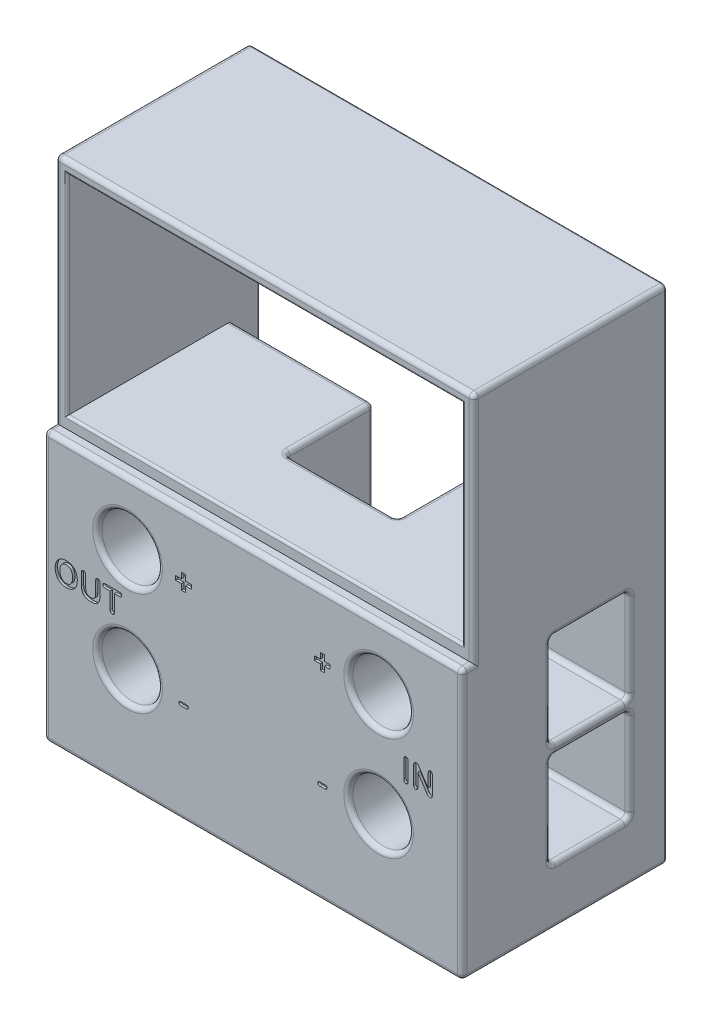
SolidWorks part; units mm, degrees
ref_plane "Front Plane" through (0, 0, 0) normal (0, 0, 1) x (1, 0, 0)
ref_plane "Top Plane" through (0, 0, 0) normal (0, 1, 0) x (1, 0, 0)
ref_plane "Right Plane" through (0, 0, 0) normal (1, 0, 0) x (0, 0, -1)
sketch "Sketch2" plane through (0, 0, 0) normal (0, 0, 1) x (1, 0, 0)
  line L0 (0, 32.5) -> (0, 0) construction
  line L1 (43.9999, -54) -> (-43.9999, -54)
  line L2 (43.9999, -54) -> (43.9999, 54)
  line L3 (43.9999, 54) -> (-43.9999, 54)
  line L4 (-43.9999, -54) -> (-43.9999, 54)
  line L5 (43.9999, -54) -> (-43.9999, 54) construction
  line L6 (43.9999, 54) -> (-43.9999, -54) construction
  line L9 (0, 0) -> (0, -20.5) construction
  line L10 (-31.75, 43.125) -> (31.75, 43.125)
  line L11 (-31.75, 43.125) -> (-31.75, 21.875)
  line L12 (-31.75, 21.875) -> (31.75, 21.875)
  line L13 (31.75, 43.125) -> (31.75, 21.875)
  line L14 (-31.75, 43.125) -> (31.75, 21.875) construction
  line L15 (-31.75, 21.875) -> (31.75, 43.125) construction
  line L16 (27, -31.625) -> (-27, -31.625)
  line L17 (27, -31.625) -> (27, -9.375)
  line L18 (27, -9.375) -> (-27, -9.375)
  line L19 (-27, -31.625) -> (-27, -9.375)
  line L20 (27, -31.625) -> (-27, -9.375) construction
  line L21 (27, -9.375) -> (-27, -31.625) construction
  circle A0 centre (-27, -9.375) radius 6.5
  circle A1 centre (27, -9.375) radius 6.5
  circle A2 centre (27, -31.625) radius 6.5
  circle A3 centre (-27, -31.625) radius 6.5
  point P0 (0, 0)
  point P5 (0, 32.5)
  point P26 (0, -20.5)
  dimension "D4" = 13
  dimension "D1" = 108
  dimension "D2" = 21.25
  dimension "D3" = 63.5
  dimension "D5" = 22.25
  dimension "D6" = 54
  dimension "D7" = 87.9997
  dimension "D8" = 32.5
  dimension "D9" = 20.5
extrude "Boss-Extrude1" add sketch "Sketch2" against normal blind 46 contours L4 L1 L2 L3 A3 L19 A0 L18 A1 L17 A2 L16 L10 L13 L12 L11 | A3 L16 A2 L17 A1 L18 A0 L19 region at (0, -1.6874, 0) region at (0, -20.5, 0)
sketch "Sketch3" plane through (0, 0, 0) normal (1, 0, 0) x (0, 0, -1)
  line L0 (46, -54) -> (0, -54) construction
  line L1 (46, 54) -> (0.0001, 54)
  line L2 (46, 54) -> (46, -54)
  line L3 (46, -54) -> (0.0001, -54)
  line L4 (0.0001, 54) -> (0.0001, -54)
  line L5 (46, 54) -> (0.0001, -54) construction
  line L6 (46, -54) -> (0.0001, 54) construction
  line L7 (46, -54) -> (46, 54) construction
  line L8 (23, -15.875) -> (23, -25.125) construction
  line L9 (30.5308, -2.875) -> (30.5308, -15.875) construction
  line L18 (34, 0.625) -> (34, -19.375)
  line L19 (34, -9.375) -> (27.5, -9.375) construction
  line L20 (36, -19.375) -> (34, -19.375)
  line L21 (36, 0.625) -> (36, -19.375)
  line L22 (36, 0.625) -> (34, 0.625)
  line L23 (34, -19.375) -> (34, 0.625)
  line L24 (19, 0.625) -> (34, 0.625)
  line L25 (19, -19.375) -> (19, 0.625)
  line L26 (19, -19.375) -> (34, -19.375)
  line L27 (46, -2.875) -> (0, -2.875) construction
  line L28 (0, -15.875) -> (46, -15.875) construction
  line L29 (46, -25.125) -> (0, -25.125) construction
  line L30 (0.0001, -20.5) -> (46, -20.5) construction
  line L31 (34, -31.625) -> (27.5, -31.625) construction
  line L32 (30.5308, -38.125) -> (30.5308, -25.125) construction
  line L33 (19, -21.625) -> (34, -21.625)
  line L34 (19, -21.625) -> (19, -41.625)
  line L35 (19, -41.625) -> (34, -41.625)
  line L36 (34, -21.625) -> (34, -41.625)
  line L37 (36, -41.625) -> (34, -41.625)
  line L38 (36, -41.625) -> (36, -21.625)
  line L39 (36, -21.625) -> (34, -21.625)
  line L40 (34, -41.625) -> (34, -21.625)
  arc A1 (34, -17.625) -> (34, -1.125) centre (35.9856, -9.375) cw
  arc A2 (34, -23.375) -> (34, -39.875) centre (35.9856, -31.625) ccw
  point P0 (23, 0)
  point P8 (30.5308, -9.375)
  point P19 (23, -20.5)
  point P48 (23, -41)
  dimension "D4" = 6.5
  dimension "D7" = 1.75
  dimension "D1" = 108
  dimension "D2" = 20
  dimension "D3" = 45.9999
  dimension "D5" = 2
  dimension "D6" = 15
  dimension "D8" = 10
sketch "Sketch4" plane through (0, 0, -46) normal (0, 0, -1) x (-1, 0, 0)
  line L1 (-31.75, 21.875) -> (31.75, 21.875)
  line L2 (-31.75, 21.875) -> (-31.75, 43.125)
  line L3 (-31.75, 43.125) -> (31.75, 43.125)
  line L4 (31.75, 21.875) -> (31.75, 43.125)
extrude "Boss-Extrude2" add sketch "Sketch4" against normal offset from surface (44 mm away) 2 up to face at (-20.5, -9.375, 0)
sketch "Sketch5" plane through (0, 0, -46) normal (0, 0, -1) x (-1, 0, 0)
  circle A0 centre (-27, -9.375) radius 6.5
  circle A1 centre (-27, -31.625) radius 6.5
  circle A2 centre (27, -31.625) radius 6.5
  circle A3 centre (27, -9.375) radius 6.5
  circle A5 centre (-27, -9.375) radius 6.5 construction
extrude "Boss-Extrude3" add sketch "Sketch5" against normal blind 10
sketch "Sketch7" plane through (0, 0, 0) normal (0, 0, 1) x (1, 0, 0)
  line L0 (-45, -54) -> (45, 54) construction
  line L1 (-45, 54) -> (45, 54)
  line L2 (-45, 54) -> (-45, -54)
  line L3 (-45, -54) -> (45, -54)
  line L4 (45, 54) -> (45, -54)
  line L5 (43.9999, 54) -> (-43.9999, 54) construction
  line L7 (-43.9999, 54) -> (43.9999, 54)
  line L8 (-43.9999, 54) -> (-43.9999, -54)
  line L9 (-43.9999, -54) -> (43.9999, -54)
  line L10 (43.9999, 54) -> (43.9999, -54)
  line M10 (-43.9999, 54) -> (-43.9999, -54)
  line M12 (43.9999, -54) -> (43.9999, 54)
  dimension "D1" = 90
extrude "Boss-Extrude4" add sketch "Sketch7" against normal up to surface (46 mm away) contours L0 L3 L4 M12 | L2 L0 L1 M10 | L10 L0 L1 | L0 L3 L8 region at (-44.5009, 0.2995, 0) region at (-44.3332, -53.5999, 0) region at (44.3332, 53.5999, 0) region at (44.5009, -0.2995, 0) up to face at (0, 0, -46)
extrude "Cut-Extrude1" cut sketch "Sketch3" along normal blind 28 from surface contours L18 A1 L24 L25 L26 | L21 L22 L18 L23 L20 | A2 L36 L33 L34 L35 | L40 A2 | L38 L39 L36 L40 L37 | A1 L23 region at (0, -9.375, -35) region at (0, -9.375, -24.7667) region at (0, -9.375, -31.2897) region at (0, -31.625, -24.7667) region at (0, -31.625, -35) region at (0, -31.625, -31.2897) starting at face at (-45, 0, -23)
extrude "Cut-Extrude2" cut sketch "Sketch3<3>" against normal blind 28 from surface contours L18 A1 L24 L25 L26 | A1 L23 | L21 L22 L18 L23 L20 | L38 L39 L36 L40 L37 | L40 A2 | A2 L36 L33 L34 L35 region at (0, -9.375, -35) region at (0, -9.375, -24.7667) region at (0, -9.375, -31.2897) region at (0, -31.625, -24.7667) region at (0, -31.625, -35) region at (0, -31.625, -31.2897) starting at face at (45, 0, -23)
sketch "Sketch3<3>" plane through (0, 0, 0) normal (1, 0, 0) x (0, 0, -1) same geometry as "Sketch3"
sketch "Sketch6" plane through (0, 0, 0) normal (0, 0, 1) x (1, 0, 0)
  line L1 (-42.5, 51.5) -> (42.5, 51.5)
  line L2 (-42.5, 51.5) -> (-42.5, 6.5)
  line L3 (-42.5, 6.5) -> (42.5, 6.5)
  line L4 (42.5, 51.5) -> (42.5, 6.5)
  line L5 (-42.5, 51.5) -> (42.5, 6.5) construction
  line L6 (-45, 54) -> (45, 54)
  line L7 (-45, 54) -> (-45, 4)
  line L8 (-45, 4) -> (45, 4)
  line L9 (45, 54) -> (45, 4)
  line L10 (45, 54) -> (-45, 4) construction
  point P9 (0, 29)
  line M13 (-31.75, 43.125) -> (31.75, 43.125)
  line M14 (31.75, 43.125) -> (31.75, 21.875)
  line M15 (31.75, 21.875) -> (-31.75, 21.875)
  line M16 (-31.75, 21.875) -> (-31.75, 43.125)
  dimension "D1" = 85
  dimension "D2" = 45
  dimension "D3" = 90
  dimension "D4" = 50
extrude "Cut-Extrude4" cut sketch "Sketch6" against normal through all contours L4 L1 L2 L3 M16 M13 M14 M15 | M13 M16 M15 M14 region at (0, 50.5382, 0) region at (0, 32.5, 0)
sketch "Sketch8" plane through (0, 0, -36) normal (0, 0, 1) x (1, 0, 0)
  circle A0 centre (-27, -9.375) radius 4.25
  circle A1 centre (-27, -31.625) radius 4.25
  circle A2 centre (27, -31.625) radius 4.25
  circle A3 centre (27, -9.375) radius 4.25
  circle A4 centre (27, -31.625) radius 6.5 construction
  circle A5 centre (27, -9.375) radius 6.5 construction
  circle A6 centre (-27, -9.375) radius 6.5 construction
  circle A7 centre (-27, -31.625) radius 6.5 construction
  dimension "D1" = 8.5
extrude "Cut-Extrude5" cut sketch "Sketch8" against normal through all
sketch "Sketch9" plane through (0, 0, -46) normal (0, 0, -1) x (-1, 0, 0)
  line L0 (0, -51.5) -> (0, -54) construction
  line L1 (-42.5, 51.5) -> (42.5, 51.5)
  line L2 (-42.5, 51.5) -> (-42.5, -51.5)
  line L3 (-42.5, -51.5) -> (42.5, -51.5)
  line L4 (42.5, 51.5) -> (42.5, -51.5)
  line L5 (-45, -54) -> (45, -54) construction
  line L6 (42.5, 0) -> (45, 0) construction
  line L7 (45, -54) -> (45, 54) construction
extrude "Cut-Extrude6" cut sketch "Sketch9" against normal blind 8
extrude "Cut-Extrude7" cut sketch "Sketch6<4>" against normal blind 2.5
sketch "Sketch6<4>" plane through (0, 0, 0) normal (0, 0, 1) x (1, 0, 0) same geometry as "Sketch6"
sketch "Sketch10" plane through (0, 0, 0) normal (1, 0, 0) x (0, 0, -1)
  line L0 (46, -54) -> (0, -54) construction
  line L1 (46, 54) -> (44, 54)
  line L2 (46, 54) -> (46, -54)
  line L3 (46, -54) -> (44, -54)
  line L4 (44, 54) -> (44, -54)
  dimension "D1" = 2
extrude "Cut-Extrude8" cut sketch "Sketch10" against normal through all both and the other way through all
fillet "Fillet2" radius 1 74 edges at (-45, -41.625, -27.5) (-45, -21.625, -27.5) (-45, -19.375, -27.5) (-45, 0.625, -27.5) (-17, -19.375, -27.5) (-17, 0.625, -27.5) (-31, -21.625, -36) (-31, -41.625, -36) (-45, -31.625, -36) (-22.75, -31.625, -36) (-31, 0.625, -36) (-17, -9.375, -36) (-31, -19.375, -36) (-45, -9.375, -36) (-22.75, -9.375, -36) (-17, -41.625, -27.5) (-17, -31.625, -36) (-17, -21.625, -27.5) (-27, -38.125, -19) (-31, -41.625, -19) (-17, -31.625, -19) (-31, -21.625, -19) (-45, -31.625, -19) (-27, -2.875, -19) (-31, -19.375, -19) (-17, -9.375, -19) (-31, 0.625, -19) (-45, -9.375, -19) (45, -19.375, -27.5) (27, -2.875, -19) (31, -19.375, -19) (45, -9.375, -19) (17, -19.375, -27.5) (17, -9.375, -19) (17, 0.625, -27.5) (31, 0.625, -19) (45, 0.625, -27.5) (31, -19.375, -36) (17, -9.375, -36) (31, 0.625, -36) (45, -9.375, -36) (31.25, -9.375, -36) (45, -41.625, -27.5) (31, -41.625, -36) (45, -31.625, -36) (31.25, -31.625, -36) (31, -21.625, -36) (45, -21.625, -27.5) (27, -38.125, -19) (31, -21.625, -19) (31, -41.625, -19) (45, -31.625, -19) (17, -31.625, -19) (17, -21.625, -27.5) (17, -31.625, -36) (17, -41.625, -27.5) (0, 6.5, -38) (45, -54, -22) (-45, -54, -22) (-45, 54, -23.25) (-45, 4, -1.25) (-45, 29, -2.5) (-45, -25, 0) (0, -54, 0) (0, 4, 0) (45, 4, -1.25) (45, -25, 0) (45, 54, -23.25) (45, 29, -2.5) (0, 54, -2.5) (-20.5, -31.625, 0) (33.5, -9.375, 0) (33.5, -31.625, 0) (-20.5, -9.375, 0)
fillet "Fillet3" radius 0.5 20 edges at (44.7071, 53.7071, -44) (0, 54, -44) (-44.7071, 53.7071, -44) (-45, 0, -44) (-44.7071, -53.7071, -44) (0, -54, -44) (44.7071, -53.7071, -44) (45, 0, -44) (42.5, 0, -44) (0, -51.5, -44) (-42.5, 0, -44) (0, 51.5, -44) (-31.25, -31.625, -38) (22.75, -9.375, -38) (22.75, -31.625, -38) (-31.25, -9.375, -38) (-42.5, 29, -2.5) (0, 6.5, -2.5) (42.5, 29, -2.5) (0, 51.5, -2.5)
sketch "Sketch11" plane through (0, 0, -38) normal (0, 0, -1) x (-1, 0, 0)
  line L0 (-42.5, 6.5) -> (42.5, 6.5) construction
  line L1 (-12, 6.5) -> (12, 6.5)
  line L2 (-12, 6.5) -> (-12, -51.5)
  line L3 (-12, -51.5) -> (12, -51.5)
  line L4 (12, 6.5) -> (12, -51.5)
  line L5 (-12, 6.5) -> (12, -51.5) construction
  line L6 (-12, -51.5) -> (12, 6.5) construction
  line L7 (-42.5, -51.5) -> (42.5, -51.5) construction
  line L8 (0, -22.5) -> (0, 0) construction
  line L9 (-17, -0.375) -> (-17, -18.375) construction
  point P0 (0, -22.5)
  dimension "D1" = 5
extrude "Cut-Extrude9" cut sketch "Sketch11" against normal up to surface (19 mm away) up to face at (-27, -1.875, -19)
fillet "Fillet4" radius 1 10 edges at (12, -23, -38) (-12, -23, -38) (12, 6.2071, -37.7071) (-12, 6.2071, -37.7071) (12, 6.5, -28) (-12, 6.5, -28) (0, -51.5, -19) (12, -22.5, -19) (0, 6.5, -19) (-12, -22.5, -19)
sketch "Sketch12" plane through (0, 0, 0) normal (0, 0, 1) x (1, 0, 0)
  line L0 (-27, -9.375) -> (-27, -31.625) construction
  line L1 (-19.5, -9.375) -> (-19.5, -31.625) construction
  line L4 (-19.5, -20.5) -> (-44, -20.5) construction
  line L5 (-44, 3) -> (-44, -53) construction
  line L6 (-27, -9.375) -> (-19.5, -9.375) construction
  line L7 (-44, -23) -> (-27, -23) construction
  line L8 (27, -9.375) -> (27, -31.625) construction
  line L9 (-19.9289, -11.875) -> (-9.9289, -11.875) construction
  line L11 (-19.5, -9.375) -> (27, -9.375) construction
  line L12 (-19.5, -31.625) -> (27, -31.625) construction
  line L13 (-9.9289, -11.875) -> (9.9289, -11.875) construction
  line L14 (-19.9289, -34.125) -> (-9.9289, -34.125) construction
  line L15 (-19.9289, -11.875) -> (-19.9289, -34.125) construction
  line L16 (-27, -23) -> (27, -23) construction
  line L17 (27, -23) -> (44, -23) construction
  line L18 (44, -53) -> (44, 3) construction
  line L19 (9.9289, -11.875) -> (19.9289, -11.875) construction
  line L20 (19.9289, -11.875) -> (19.9289, -34.125) construction
  line L21 (-9.9289, -34.125) -> (9.9289, -34.125) construction
  line L22 (9.9289, -34.125) -> (19.9289, -34.125) construction
  line L23 (0, -11.875) -> (0, -34.125) construction
  circle A0 centre (-27, -9.375) radius 7.5 construction
  circle A1 centre (-27, -31.625) radius 7.5 construction
  circle A2 centre (27, -31.625) radius 7.5 construction
  circle A4 centre (27, -9.375) radius 7.5 construction
  text T0 "OUT" font "Arial Rounded MT Bold" height 5
  text T1 "IN" font "Arial Rounded MT Bold" height 5
  text T2 "+" font "Arial Rounded MT Bold" height 5
  text T3 "-" font "Arial Rounded MT Bold" height 5
  text T4 "+" font "Arial Rounded MT Bold" height 5
  text T5 "-" font "Arial Rounded MT Bold" height 5
  point P10 (-27, -20.5)
  point P41 (-9.7727, -11.875)
  point P42 (5.4806, -11.875)
  point P43 (6.1395, -11.875)
  dimension "D1" = 2.5
  dimension "D2" = 2.5
  dimension "D3" = 10
  dimension "D4" = 10
extrude "Cut-Extrude10" cut sketch "Sketch12" against normal blind 0.5
